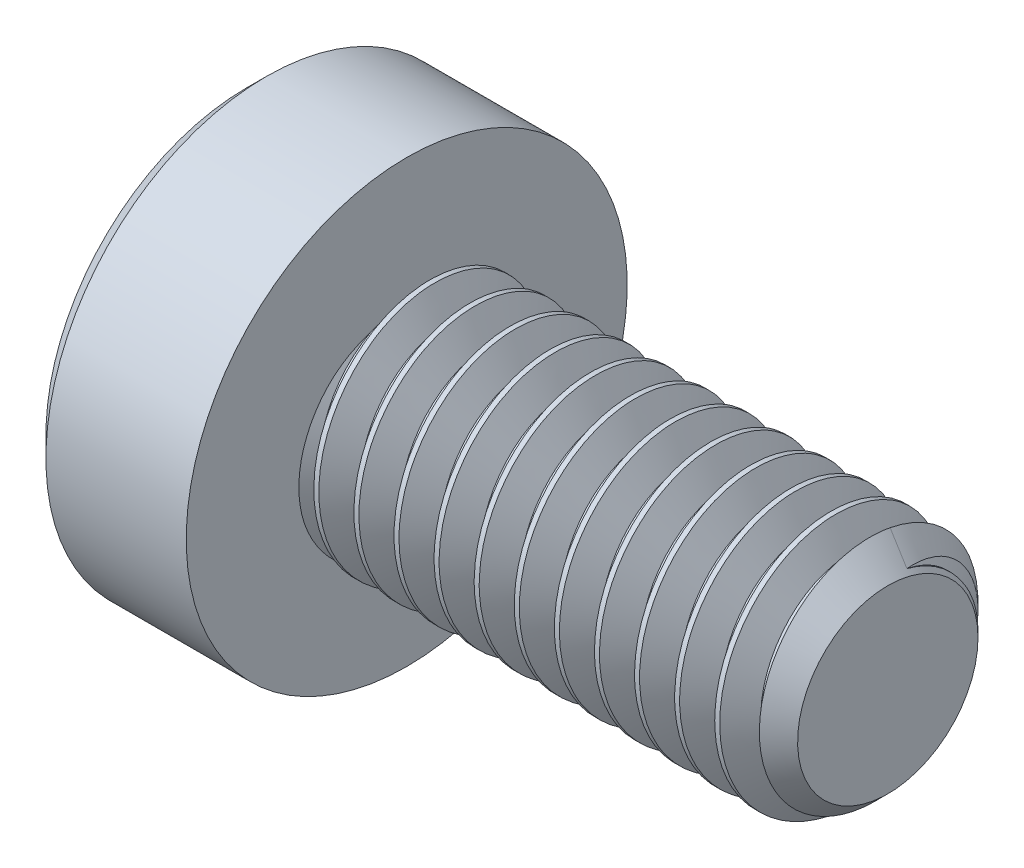
SolidWorks part; units mm, degrees
ref_plane "Front Plane" through (0, 0, 0) normal (0, 0, 1) x (1, 0, 0)
ref_plane "Top Plane" through (0, 0, 0) normal (0, 1, 0) x (1, 0, 0)
ref_plane "Right Plane" through (0, 0, 0) normal (1, 0, 0) x (0, 0, -1)
sketch "Sketch1" plane through (0, 0, 0) normal (0, 0, 1) x (1, 0, 0)
  line L0 (3, 0) -> (-3, 0) construction
  line L1 (3, 1.5) -> (3, -1.5) construction
  line L2 (-3, 2.75) -> (-3, -2.75) construction
  line L3 (-3, 2.75) -> (-4.75, 2.75) construction
  line L4 (-4.75, 2.75) -> (-5, 2.5) construction
  line L5 (-5, 2.5) -> (-5, -2.5) construction
  line L6 (-5, -2.5) -> (-4.75, -2.75) construction
  line L7 (-4.75, -2.75) -> (-3, -2.75) construction
  point P7 (-3.38, 0)
  point P12 (1, -1.5)
  dimension "D1" = 45
  dimension "Dec." = 3
  dimension "Length" = 6
  dimension "Head Dia" = 5.5
  dimension "Head Height" = 2
  dimension "Hex Depth" = 1.62
  dimension "Chamfer" = 0.25
  dimension "D2" = 2
ref_plane "Plane1" through (3, 0, 0) normal (1, 0, 0) x (0, 0, -1)
ref_plane "Plane2" through (-5, 0, 0) normal (1, 0, 0) x (0, 0, -1)
sketch "Sketch2" plane through (3, 0, 0) normal (1, 0, 0) x (0, 0, -1)
  circle A0 centre (0, 0) radius 1.5
extrude "Boss-Extrude1" add sketch "Sketch2" against normal up to vertex (6 mm away) up to point (-3, 0, 0)
sketch "Sketch3" plane through (3, 0, 0) normal (1, 0, 0) x (0, 0, -1)
  circle A0 centre (0, 0) radius 1.5 construction
  circle A1 centre (0, 0) radius 1.5
curve "Helix/Spiral1" pitch 0.5 height 6.5 radius 1.5 centre (3, 0, 0) axis (-1, 0, 0) start towards (0, 1, 0) parameters "Pitch"=0.5
chamfer "Chamfer1" distance 0.375 angle 45 1 edges at (3, 0, -1.5)
sketch "Sketch5" plane through (0, 0, 0) normal (0, 0, 1) x (1, 0, 0)
  line L0 (2.7813, 1.5) -> (3.2187, 1.5)
  line L1 (3.2187, 1.5) -> (3.0313, 1.1752)
  line L2 (3.0313, 1.1752) -> (2.9688, 1.1752)
  line L3 (2.9688, 1.1752) -> (2.7813, 1.5)
  line L4 (3, 1.1752) -> (3, 1.5) construction
  line L5 (2.875, 1.3376) -> (3.125, 1.3376) construction
  dimension "D1" = 60
  dimension "D2" = 0.25
  dimension "D3" = 0.0625
sweep "Cut-Sweep1" cut profiles "Sketch5" path "Helix/Spiral1" align with end faces yes
sketch "Sketch4" plane through (-5, 0, 0) normal (1, 0, 0) x (0, 0, -1)
  line L0 (-2.75, 0.7937) -> (2.75, 0.7937) construction
  line L1 (0, 1.1547) -> (-1, 0.5774)
  line L2 (-1, 0.5774) -> (-1, -0.5774)
  line L3 (-1, -0.5774) -> (0, -1.1547)
  line L4 (0, -1.1547) -> (1, -0.5774)
  line L5 (1, -0.5774) -> (1, 0.5774)
  line L6 (1, 0.5774) -> (0, 1.1547)
  line L7 (0, 0) -> (0, 0.7937) construction
  circle A0 centre (0, 0) radius 1 construction
  dimension "Hex Size" = 2
  dimension "D1" = 5.5
  dimension "D2" = 0.7937
sketch "Sketch6" plane through (0, 0, 0) normal (0, 0, 1) x (1, 0, 0)
  line L0 (-4.75, 2.75) -> (-5, 2.5) construction
  line L1 (-3, 2.75) -> (-4.75, 2.75) construction
  line L2 (-3, 2.75) -> (-3, -2.75) construction
  line L3 (-5, 2.5) -> (-5, -2.5) construction
  line L4 (-4.75, 2.75) -> (-5, 2.5)
  line L5 (-3, 2.75) -> (-4.75, 2.75)
  line L6 (-3, 2.75) -> (-3, 0)
  line L7 (-5, 2.5) -> (-5, 0)
  line L8 (-3, 0) -> (-5, 0) construction
  line L9 (-3, 0) -> (-5, 0)
revolve "Revolve1" add sketch "Sketch6" angle 360 about L8
extrude "Cut-Extrude1" cut sketch "Sketch4" along normal up to vertex (1.62 mm away) up to point (-3.38, 0, 0)
sketch "Sketch8" plane through (-5, 0, 0) normal (-1, 0, 0) x (0, 0, 1)
  circle A1 centre (0, 0) radius 1.1547
extrude "Cut-Extrude2" cut sketch "Sketch8" against normal through all draft 45
equation "\"D3@Helix/Spiral1\" = \"Length@Sketch1\"+\"Pitch@Helix/Spiral1\""
equation "\"D3@Sketch5\" = \"Pitch@Helix/Spiral1\"*.125"
equation "\"D2@Sketch5\" = \"Pitch@Helix/Spiral1\"*.50"
equation "\"D1@Chamfer1\" = \"Pitch@Helix/Spiral1\"*.75"
equation "\"D2@Sketch1\" = \"Pitch@Helix/Spiral1\"*4"
equation "\"D1@Sketch4\" = \"Head Dia@Sketch1\""
equation "\"Chamfer@Sketch1\" = \"Head Height@Sketch1\"/8"
